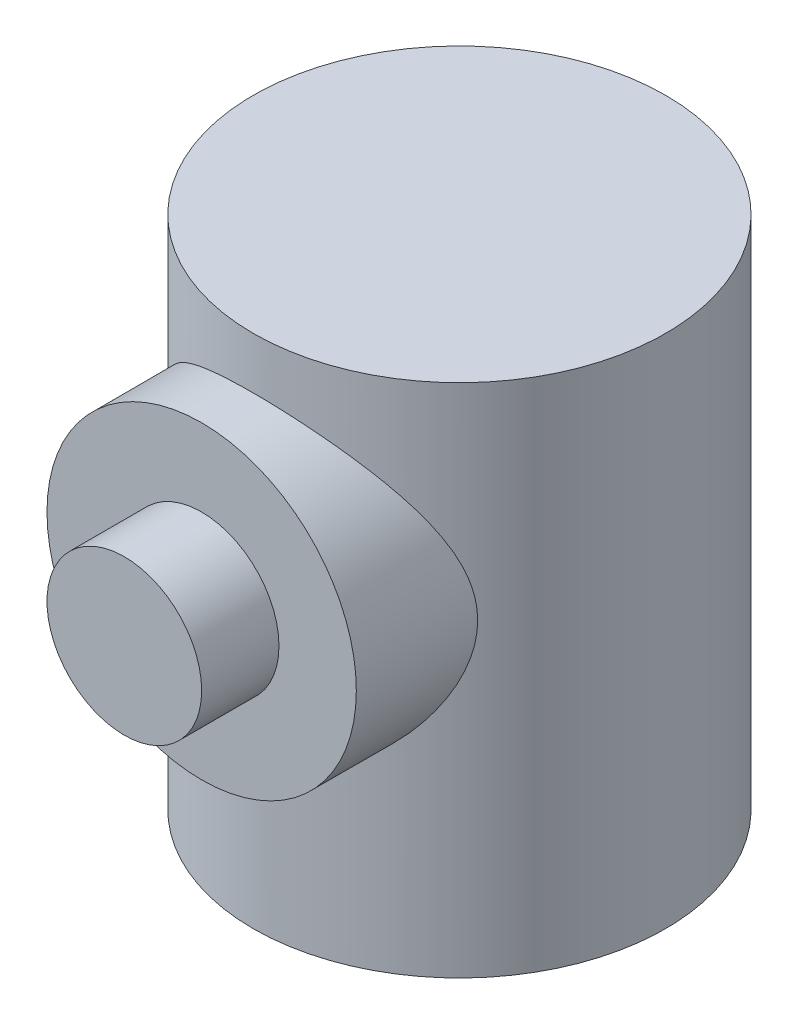
SolidWorks part; units mm, degrees
material "1060 Alloy"
ref_plane "Front Plane" through (0, 0, 0) normal (0, 0, 1) x (1, 0, 0)
ref_plane "Top Plane" through (0, 0, 0) normal (0, 1, 0) x (1, 0, 0)
ref_plane "Right Plane" through (0, 0, 0) normal (1, 0, 0) x (0, 0, -1)
sketch "Sketch1" plane through (0, 0, 0) normal (0, 1, 0) x (1, 0, 0)
  circle A0 centre (0, 0) radius 40
  circle A1 centre (0, 0) radius 15
  dimension "D1" = 80
  dimension "D2" = 30
extrude "Boss-Extrude1" add sketch "Sketch1" along normal blind 100 contours A0
sketch "Sketch2" plane through (0, 0, 0) normal (0, 0, 1) x (1, 0, 0)
  line L0 (40, 100) -> (-40, 100) construction
  circle A0 centre (0, 60) radius 30
  circle A1 centre (0, 60) radius 15
  dimension "D2" = 60
  dimension "D3" = 30
  dimension "D1" = 40
extrude "Boss-Extrude2" add sketch "Sketch2" along normal blind 50 contours A1 | A0 A1 region at (-29.1515, 60, 0) region at (0, 60, 0)
extrude "Cut-Extrude1" cut sketch "Sketch1<3>" along normal blind 15 contours A1 region at (0, 0, 0)
sketch "Sketch1<3>" plane through (0, 0, 0) normal (0, 1, 0) x (1, 0, 0) same geometry as "Sketch1"
extrude "Boss-Extrude3" add sketch "Sketch2<4>" along normal blind 15 from surface contours A1 region at (0, 60, 0) starting at face at (30, 60, 50)
sketch "Sketch2<4>" plane through (0, 0, 0) normal (0, 0, 1) x (1, 0, 0) same geometry as "Sketch2"
